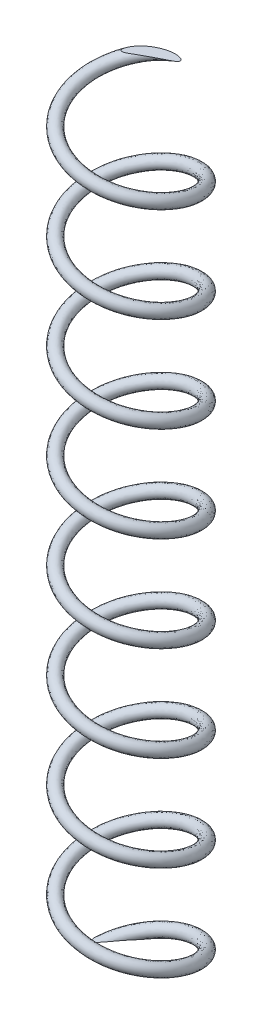
SolidWorks part; units mm, degrees
ref_plane "Front Plane" through (0, 0, 0) normal (0, 0, 1) x (1, 0, 0)
ref_plane "Top Plane" through (0, 0, 0) normal (0, 1, 0) x (1, 0, 0)
ref_plane "Right Plane" through (0, 0, 0) normal (1, 0, 0) x (0, 0, -1)
sketch "Sketch2" plane through (0, 0, 0) normal (0, 1, 0) x (1, 0, 0)
  circle A0 centre (0, 0) radius 3.5
  dimension "D1" = 7
curve "Helix/Spiral1" pitch 6.2 height 248 turns 40
ref_plane "Plane1" through (-2.4749, 0, -2.4749) normal (0.6806, 0.2714, -0.6806) x (-0.7327, 0.2521, -0.6322)
sketch "Sketch3" plane through (-2.4749, 0, -2.4749) normal (0.6806, 0.2714, -0.6806) x (-0.7327, 0.2521, -0.6322)
  circle A1 centre (-0.0014, 0.0044) radius 0.4
  dimension "D1" = 0.8
sweep "Sweep1" add profiles "Sketch3" path "Helix/Spiral1"
sketch "Sketch5" plane through (0, 0, 0) normal (0, 0, 1) x (1, 0, 0)
  line L1 (-30.2666, 149.0903) -> (30.7237, 149.0903)
  line L2 (-30.2666, 149.0903) -> (-30.2666, 99.0903)
  line L3 (-30.2666, 99.0903) -> (30.7237, 99.0903)
  line L4 (30.7237, 149.0903) -> (30.7237, 99.0903)
  dimension "D1" = 50
extrude "Cut-Extrude2" cut sketch "Sketch5" against normal mid plane 50 flip side to cut
sketch "Sketch6" plane through (0, 149.0903, 0) normal (0, 1, 0) x (1, 0, 0)
  circle A0 centre (0, 0) radius 3.904
